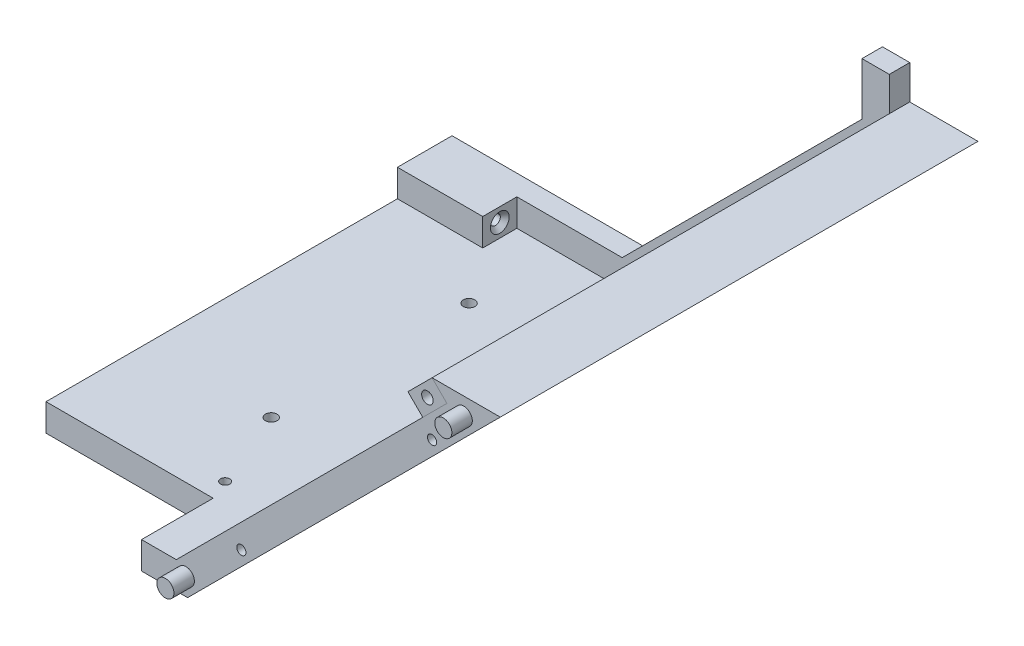
SolidWorks part; units mm, degrees
ref_plane "Plan de face" through (0, 0, 0) normal (0, 0, 1) x (1, 0, 0)
ref_plane "Plan de dessus" through (0, 0, 0) normal (0, 1, 0) x (1, 0, 0)
ref_plane "Plan de droite" through (0, 0, 0) normal (1, 0, 0) x (0, 0, -1)
sketch "Main-Sketch" plane through (0, 0, 0) normal (0, 0, 1) x (1, 0, 0)
  line L0 (0, 0) -> (62.5, 0)
  line L1 (62.5, 0) -> (154.15, 91.65)
  line L2 (154.15, 91.65) -> (134.15, 91.65)
  line L3 (134.15, 91.65) -> (138.4931, 87.3069)
  line L4 (138.4931, 87.3069) -> (59.1863, 8)
  line L5 (59.1863, 8) -> (0, 8)
  line L6 (0, 8) -> (0, 0)
  dimension "D1" = 8
  dimension "D2" = 8
  dimension "D3" = 20
  dimension "D4" = 135
  dimension "D5" = 154.15
  dimension "D6" = 62.5
extrude "Main-Extrusion" add sketch "Main-Sketch" along normal blind 140
sketch "Lcd-Hole-Sketch" plane through (0, 8, 0) normal (0, 1, 0) x (-1, 0, 0)
  line L1 (0, 140) -> (-49, 140)
  line L2 (0, 140) -> (0, 119)
  line L3 (0, 119) -> (-49, 119)
  line L4 (-49, 140) -> (-49, 119)
  dimension "D1" = 21
  dimension "D2" = 49
extrude "Lcd-Hole" cut sketch "Lcd-Hole-Sketch" against normal through all
sketch "Lcd-Fix-Sketch" plane through (0, 8, 0) normal (0, 1, 0) x (1, 0, 0)
  line L1 (49, -119) -> (0, -119) construction
  line L2 (49, -140) -> (49, -119) construction
  circle A0 centre (46.5, -113) radius 1.35
  dimension "D1" = 2.7
  dimension "D2" = 2.5
  dimension "D3" = 6
extrude "Lcd-Fix" cut sketch "Lcd-Fix-Sketch" against normal blind 7
sketch "Bottom-Reinforcement-Sketch" plane through (0, 0, 0) normal (0, 0, 1) x (1, 0, 0)
  line L0 (59.1863, 8) -> (138.4931, 87.3069)
  line L1 (134.15, 101.65) -> (126.15, 101.65)
  line L2 (126.15, 101.65) -> (126.15, 86.2774)
  line L5 (138.4931, 87.3069) -> (59.1863, 8) construction
  line L6 (134.15, 91.65) -> (134.15, 101.65)
  line L7 (59.1863, 8) -> (0, 8)
  line L8 (0, 0) -> (0, 8) construction
  line L9 (0, 8) -> (0, 16)
  line L10 (0, 16) -> (55.8726, 16)
  line L11 (55.8726, 16) -> (126.15, 86.2774)
  line L13 (138.4931, 87.3069) -> (134.15, 91.65)
  dimension "D1" = 8
  dimension "D2" = 10
  dimension "D3" = 8
  dimension "D4" = 8
extrude "Bottom-Reinforcement-Extrusion" add sketch "Bottom-Reinforcement-Sketch" along normal blind 6 separate body
sketch "Power-Board-Hole-Sketch" plane through (22.1744, -40.3256, 188.8128) normal (0.7071, -0.7071, 0) x (0, 0, -1)
  line L1 (150.8128, 154.6417) -> (68.8128, 154.6417)
  line L2 (150.8128, 154.6417) -> (150.8128, 80.029)
  line L3 (150.8128, 80.029) -> (68.8128, 80.029)
  line L4 (68.8128, 154.6417) -> (68.8128, 80.029)
  line L6 (188.8128, 57.029) -> (188.8128, 186.6417) construction
  line L7 (48.8128, 57.029) -> (48.8128, 186.6417) construction
  line L8 (48.8128, 57.029) -> (188.8128, 57.029) construction
  line L9 (48.8128, 186.6417) -> (188.8128, 186.6417) construction
  dimension "D1" = 20
  dimension "D2" = 38
  dimension "D3" = 32
  dimension "D4" = 23
extrude "Power-Board-Hole" cut sketch "Power-Board-Hole-Sketch" against normal through all
sketch "Power-Board-Window-Sketch" plane through (22.1744, -40.3256, 188.8128) normal (0.7071, -0.7071, 0) x (0, 0, -1)
  line L0 (150.8128, 80.029) -> (150.8128, 154.6417) construction
  line L1 (156.8128, 160.6417) -> (62.8128, 160.6417)
  line L2 (156.8128, 160.6417) -> (156.8128, 74.029)
  line L3 (156.8128, 74.029) -> (62.8128, 74.029)
  line L4 (62.8128, 160.6417) -> (62.8128, 74.029)
  line L5 (150.8128, 154.6417) -> (68.8128, 154.6417) construction
  line L6 (68.8128, 154.6417) -> (68.8128, 80.029) construction
  line L7 (68.8128, 80.029) -> (150.8128, 80.029) construction
  dimension "D1" = 6
  dimension "D2" = 6
  dimension "D3" = 6
  dimension "D4" = 6
extrude "Power-Board-Window" cut sketch "Power-Board-Window-Sketch" against normal blind 5
sketch " Power-Board-Window-Fix-Sketch" plane through (27.7145, -27.7145, 0) normal (0.7071, -0.7071, 0) x (0, 0, -1)
  line L0 (-38, 67.1942) -> (-38, 141.8068) construction
  line L1 (-38, 141.8068) -> (-120, 141.8068) construction
  line L2 (-120, 67.1942) -> (-38, 67.1942) construction
  line L3 (-120, 141.8068) -> (-120, 67.1942) construction
  circle A0 centre (-123, 104.5005) radius 1.35
  circle A1 centre (-35, 104.5005) radius 1.35
  circle A2 centre (-79, 144.8068) radius 1.35
  circle A3 centre (-79, 64.1942) radius 1.35
  point P11 (-38, 104.5005)
  point P15 (-79, 141.8068)
  point P19 (-79, 67.1942)
  point P22 (-120, 104.5005)
  dimension "D1" = 2.7
  dimension "D2" = 3
  dimension "D3" = 3
  dimension "D4" = 3
  dimension "D5" = 3
extrude "Power-Board-Window-Fix" cut sketch " Power-Board-Window-Fix-Sketch" against normal through all
sketch "PowerBoard-Fix-Sketch" plane through (25.5931, -25.5931, 0) normal (-0.7071, 0.7071, 0) x (0, 0, 1)
  line L0 (140, 159.6647) -> (0, 159.6647) construction
  line L2 (6, 47.5079) -> (6, 159.6647) construction
  circle A0 centre (13, 137.6647) radius 4
  circle A1 centre (11, 68.6647) radius 4
  dimension "D1" = 8
  dimension "D2" = 8
  dimension "D3" = 22
  dimension "D4" = 69
  dimension "D5" = 7
  dimension "D6" = 5
extrude "PowerBoard-Fix-Extrusion" add sketch "PowerBoard-Fix-Sketch" along normal blind 5
sketch "PowerBoard-Fix-Hole-Sketch" plane through (22.0576, -22.0576, 0) normal (-0.7071, 0.7071, 0) x (0, 0, 1)
  circle A0 centre (13, 137.6647) radius 1.35
  circle A1 centre (11, 68.6647) radius 1.35
  dimension "D1" = 2.7
extrude "PowerBoard-Fix-Hole" cut sketch "PowerBoard-Fix-Hole-Sketch" against normal through all
sketch "Top-Fix-Sketch" plane through (0, 0, 140) normal (0, 0, 1) x (1, 0, 0)
  line L0 (62.5, 0) -> (154.15, 91.65) construction
  line L1 (49, 0) -> (49, 8) construction
  line L2 (134.15, 91.65) -> (138.4931, 87.3069) construction
  circle A0 centre (62, 5.1569) radius 2.5
  circle A1 centre (143.4462, 86.5965) radius 2.5
  point P12 (49, 4)
  dimension "D1" = 5
  dimension "D2" = 5
  dimension "D4" = 4
  dimension "D5" = 3.9954
  dimension "D6" = 13
  dimension "D7" = 3
extrude "Top-Fix" add sketch "Top-Fix-Sketch" along normal blind 6
sketch "Top-Fix-Hole-Sketch" plane through (0, 0, 140) normal (0, 0, 1) x (1, 0, 0)
  line L0 (62.5, 0) -> (154.15, 91.65) construction
  circle A0 centre (78.2574, 20) radius 1.35
  circle A1 centre (134.15, 75.8926) radius 1.35
  dimension "D1" = 2.7
  dimension "D2" = 2.7
  dimension "D3" = 3
  dimension "D4" = 3
  dimension "D5" = 20
  dimension "D6" = 20
extrude "Top-Fix-Hole" cut sketch "Top-Fix-Hole-Sketch" against normal blind 30
sketch "Esquisse3" plane through (0, 0, 140) normal (0, 0, 1) x (1, 0, 0)
  line L0 (138.4931, 87.3069) -> (134.15, 91.65)
  line L1 (134.15, 91.65) -> (127.0789, 84.5789)
  line L2 (127.0789, 84.5789) -> (131.4221, 80.2358)
  line L3 (138.4931, 87.3069) -> (59.1863, 8) construction
  line L4 (131.4221, 80.2358) -> (138.4931, 87.3069)
  dimension "D1" = 10
extrude "Boss.-Extru.2" add sketch "Esquisse3" against normal blind 10 separate body
hole_wizard "Fraisage pour vis à tête fraisée M31" positions "Esquisse5" profile "Esquisse4" countersink size "M3" standard "Ansi Metric" end condition up to next
sketch "Esquisse5" plane through (0, 0, 130) normal (0, 0, -1) x (-1, 0, 0)
  line L0 (-127.0789, 84.5789) -> (-131.4221, 80.2358) construction
  line L1 (-134.15, 91.65) -> (-127.0789, 84.5789) construction
  point P0 (-132.7853, 85.9436)
  dimension "D1" = 5
  dimension "D2" = 3.07
sketch "Esquisse4" plane through (132.7853, 85.9436, 130) normal (1, 0, 0) x (0, 1, 0)
  line L0 (0, 0) -> (0, 10.001)
  line L1 (0, 10.001) -> (1.7, 10.001)
  line L2 (1.7, 10.001) -> (1.7, 1.3)
  line L3 (1.7, 1.3) -> (3, 0)
  line L5 (3, 0) -> (0, 0)
  line L6 (-1.7, 1.3) -> (-3, 0) construction
  line L11 (0, -6.35) -> (0, 107.95) construction
  dimension "Diamètre du perçage jusqu'au prochain" = 3.4
  dimension "Profondeur du perçage jusqu'au prochain" = 10.001
  dimension "Diamètre du fraisage entrant" = 6
  dimension "Angle du fraisage entrant" = 90
sketch "Fix-Sketch" plane through (0, 0, 0) normal (-1, 0, 0) x (0, 0, 1)
  line L0 (119, 0) -> (119, 8) construction
  circle A0 centre (104, 4) radius 2.5
  circle A1 centre (74, 4) radius 2.5
  circle A2 centre (44, 4) radius 2.5
  circle A3 centre (14, 4) radius 2.5
  point P10 (119, 4)
  dimension "D2" = 5
  dimension "D1" = 15
  dimension "D3" = 30
  dimension "D4" = 30
  dimension "D5" = 30
extrude "Fix-Hole" cut sketch "Fix-Sketch" against normal blind 10
ref_plane "EndOfFix-Plan" through (15, 0, 0) normal (-1, 0, 0) x (0, 0, 1)
ref_axis "EndOfFix-Axe" through (15, -0.8, 6) along (0, 1, 0)
ref_plane "EndOFix-Inclined-Plan" through (15.4952, 0, 4.1519) normal (-0.9659, 0, -0.2588) x (0, 1, 0)
sketch "Bottom-Fix-Sketch" plane through (0, 0, 0) normal (-1, 0, 0) x (0, 0, 1)
  line L0 (0, 12.5) -> (6, 11.5)
  line L1 (6, 16) -> (6, 8) construction
  line L2 (6, 11.5) -> (6, 3.5)
  line L3 (6, 3.5) -> (0, 2.5)
  line L4 (0, 8) -> (0, 0) construction
  line L5 (0, 2.5) -> (0, 12.5)
  line L8 (0, 16) -> (0, 8) construction
  point P12 (6, 7.5)
  point P13 (0, 7.5)
  dimension "D1" = 2.5
  dimension "D2" = 8
  dimension "D3" = 10
  dimension "D4" = 3.5
extrude "Bottom-Fix-Extrusion" cut sketch "Bottom-Fix-Sketch" against normal up to surface (16.6077 mm away) up to plane "EndOFix-Inclined-Plan"
sketch "Bottom-Fix-Reinforcement-Sketch" plane through (0, 8, 0) normal (0, 1, 0) x (1, 0, 0)
  line L0 (15, -6) -> (59.1863, -6) construction
  line L1 (0, -16) -> (25, -16)
  line L2 (0, -16) -> (0, -6)
  line L3 (0, -6) -> (25, -6)
  line L4 (25, -16) -> (25, -6)
  line L5 (0, -119) -> (0, -6) construction
  dimension "D1" = 25
  dimension "D2" = 10
extrude "Bottom-Fix-Reinforcement-Extrusion" add sketch "Bottom-Fix-Reinforcement-Sketch" along normal up to surface (8 mm away) up to face at (27.9363, 16, 3)
hole_wizard "Fraisage pour vis à tête fraisée M2.51" positions "Esquisse10" profile "Esquisse9" countersink size "M2.5" standard "Ansi Metric" end condition through all
sketch "Esquisse10" plane through (25, 0, 0) normal (1, 0, 0) x (0, 0, -1)
  line L0 (-16, 16) -> (-16, 8) construction
  line L2 (-6, 16) -> (-16, 16) construction
  point P0 (-11, 12)
  point P4 (-16, 12)
  point P10 (-11, 16)
sketch "Esquisse9" plane through (25, 12, 11) normal (0, 1, 0) x (0, 0, -1)
  line L0 (0, 0) -> (0, 25)
  line L1 (0, 25) -> (1.45, 25)
  line L2 (1.45, 25) -> (1.45, 1.3)
  line L3 (1.45, 1.3) -> (2.75, 0)
  line L5 (2.75, 0) -> (0, 0)
  line L6 (-1.45, 1.3) -> (-2.75, 0) construction
  line L11 (0, -6.35) -> (0, 107.95) construction
  dimension "Diamètre du perçage jusqu'au prochain" = 2.9
  dimension "Profondeur du perçage jusqu'au prochain" = 25
  dimension "Diamètre du fraisage entrant" = 5.5
  dimension "Angle du fraisage entrant" = 90
hole_wizard "Fraisage pour vis à tête fraisée M32" positions "Esquisse11" profile "Esquisse12" countersink size "M3" standard "Ansi Metric" end condition through all
sketch "Esquisse11" plane through (0, 0, 0) normal (0, -1, 0) x (-1, 0, 0)
  line L0 (-49, -140) -> (-62.5, -140) construction
  line L1 (0, -119) -> (0, 0) construction
  point P1 (-37, -90)
  dimension "D1" = 50
  dimension "D2" = 37
sketch "Esquisse12" plane through (37, 0, 90) normal (1, 0, 0) x (0, 0, -1)
  line L0 (0, 0) -> (0, 101.65)
  line L1 (0, 101.65) -> (1.7, 101.65)
  line L2 (1.7, 101.65) -> (1.7, 1.45)
  line L3 (1.7, 1.45) -> (3.15, 0)
  line L5 (3.15, 0) -> (0, 0)
  line L6 (-1.7, 1.45) -> (-3.15, 0) construction
  line L11 (0, -6.35) -> (0, 107.95) construction
  dimension "Diamètre du perçage jusqu'au prochain" = 3.4
  dimension "Profondeur du perçage jusqu'au prochain" = 101.65
  dimension "Diamètre du fraisage entrant" = 6.3
  dimension "Angle du fraisage entrant" = 90
pattern_linear "HDD-Fix-Linear-Repeat" count 2 spacing 58 along (0, 0, -1) of "Fraisage pour vis à tête fraisée M32"
